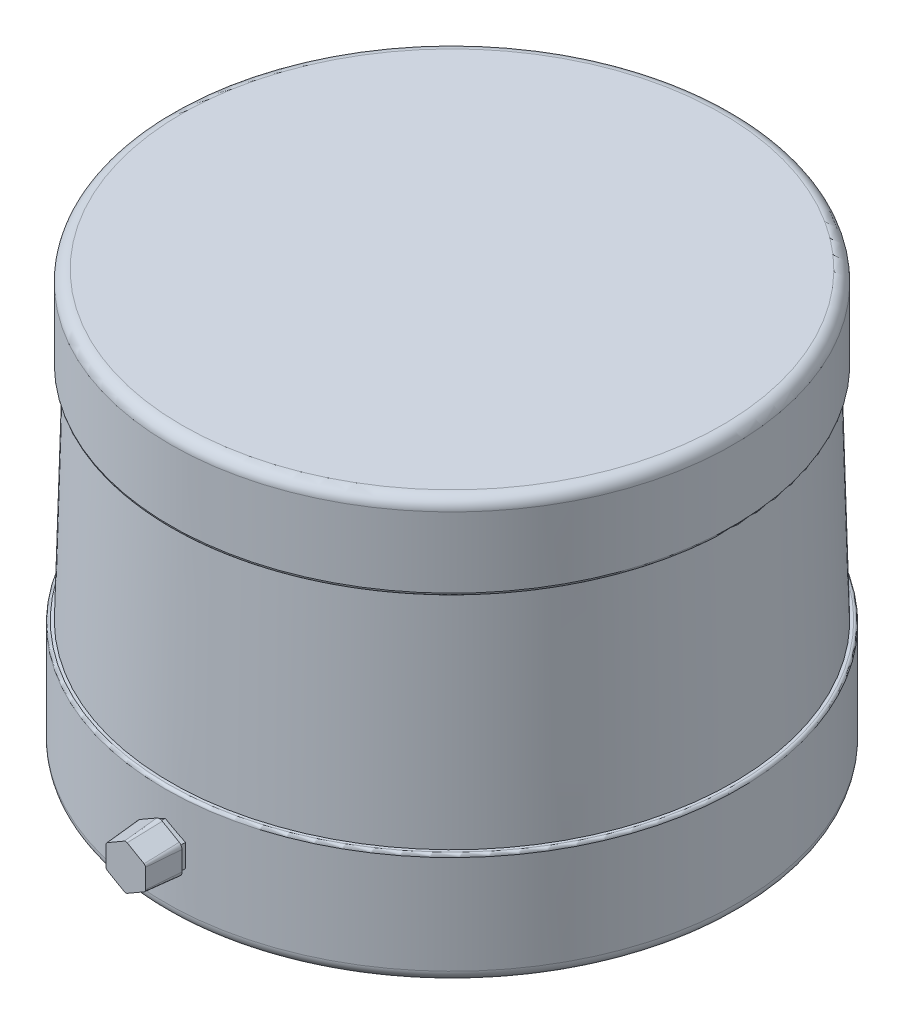
SolidWorks part; units mm, degrees
ref_plane "정면" through (0, 0, 0) normal (0, 0, 1) x (1, 0, 0)
ref_plane "윗면" through (0, 0, 0) normal (0, 1, 0) x (1, 0, 0)
ref_plane "우측면" through (0, 0, 0) normal (1, 0, 0) x (0, 0, -1)
sketch "스케치1" plane through (0, 0, 0) normal (0, 0, 1) x (1, 0, 0)
  line L0 (0, 0) -> (0, 82.7961) construction
  line L1 (0, 0) -> (51, 0)
  line L2 (51, 0) -> (51, 20)
  line L3 (51, 20) -> (50, 20)
  line L4 (50, 20) -> (49, 59)
  line L5 (49, 59) -> (50, 59)
  line L6 (50, 59) -> (50, 74)
  line L7 (50, 74) -> (0, 74)
  line L8 (0, 74) -> (0, 0)
  dimension "D1" = 74
  dimension "D2" = 51
  dimension "D3" = 50
  dimension "D4" = 20
  dimension "D5" = 15
  dimension "D6" = 1
  dimension "D7" = 1
revolve "회전1" add sketch "스케치1" angle 360 about L0
fillet "필렛1" radius 2 2 edges at (0, 0, -51) (0, 74, -50)
fillet "필렛2" radius 0.5 2 edges at (0, 20, -51) (0, 59, -50)
sketch "스케치2" plane through (0, 0, 0) normal (0, 0, 1) x (1, 0, 0)
  line L0 (0, 0) -> (0, 20) construction
  line L1 (0, 6.9171) -> (3.5, 8.9378)
  line L2 (3.5, 8.9378) -> (3.5, 12.9793)
  line L3 (3.5, 12.9793) -> (0, 15)
  line L4 (0, 15) -> (-3.5, 12.9793)
  line L5 (-3.5, 12.9793) -> (-3.5, 8.9378)
  line L6 (-3.5, 8.9378) -> (0, 6.9171)
  line L8 (50.5, 20) -> (-50.5, 20) construction
  circle A0 centre (0, 10.9585) radius 3.5 construction
  point P11 (0, 20)
  point P13 (0.1465, 19.5)
  point P14 (0, 0)
  point P15 (0, 0)
  dimension "D1" = 7
  dimension "D2" = 5
extrude "보스-돌출1" add sketch "스케치2" along normal blind 52
sketch "스케치3" plane through (0, 0, 52) normal (0, 0, 1) x (1, 0, 0)
  line L0 (-4, 8.6491) -> (0, 6.3397)
  line L1 (0, 6.3397) -> (4, 8.6491)
  line L2 (4, 8.6491) -> (4, 13.2679)
  line L3 (4, 13.2679) -> (0, 15.5774)
  line L4 (0, 15.5774) -> (-4, 13.2679)
  line L5 (-4, 13.2679) -> (-4, 8.6491)
extrude "보스-돌출2" add sketch "스케치3" along normal blind 6 contours L0 L1 L2 L3 L4 L5
fillet "필렛3" radius 1 6 edges at (0, 6.3397, 55) (-4, 8.6491, 55) (-4, 13.2679, 55) (0, 15.5774, 55) (4, 8.6491, 55) (4, 13.2679, 55)
chamfer "모따기1" distance 6 distance2 0.5 12 edges at (-2, 7.4944, 58) (0, 6.4944, 58) (-3.866, 8.7265, 58) (2, 7.4944, 58) (-4, 10.9585, 58) (3.866, 8.7265, 58) (-3.866, 13.1906, 58) (4, 10.9585, 58) (-2, 14.4226, 58) (3.866, 13.1906, 58) (0, 15.4226, 58) (2, 14.4226, 58) first distance on face at (-2, 7.4944, 55) first distance on face at (0, 6.5614, 55) first distance on face at (-3.808, 8.76, 55) first distance on face at (2, 7.4944, 55) first distance on face at (-4, 10.9585, 55) first distance on face at (3.808, 8.76, 55) first distance on face at (-3.808, 13.1571, 55) first distance on face at (4, 10.9585, 55) first distance on face at (-2, 14.4226, 55) first distance on face at (3.808, 13.1571, 55) first distance on face at (0, 15.3557, 55) first distance on face at (2, 14.4226, 55)
